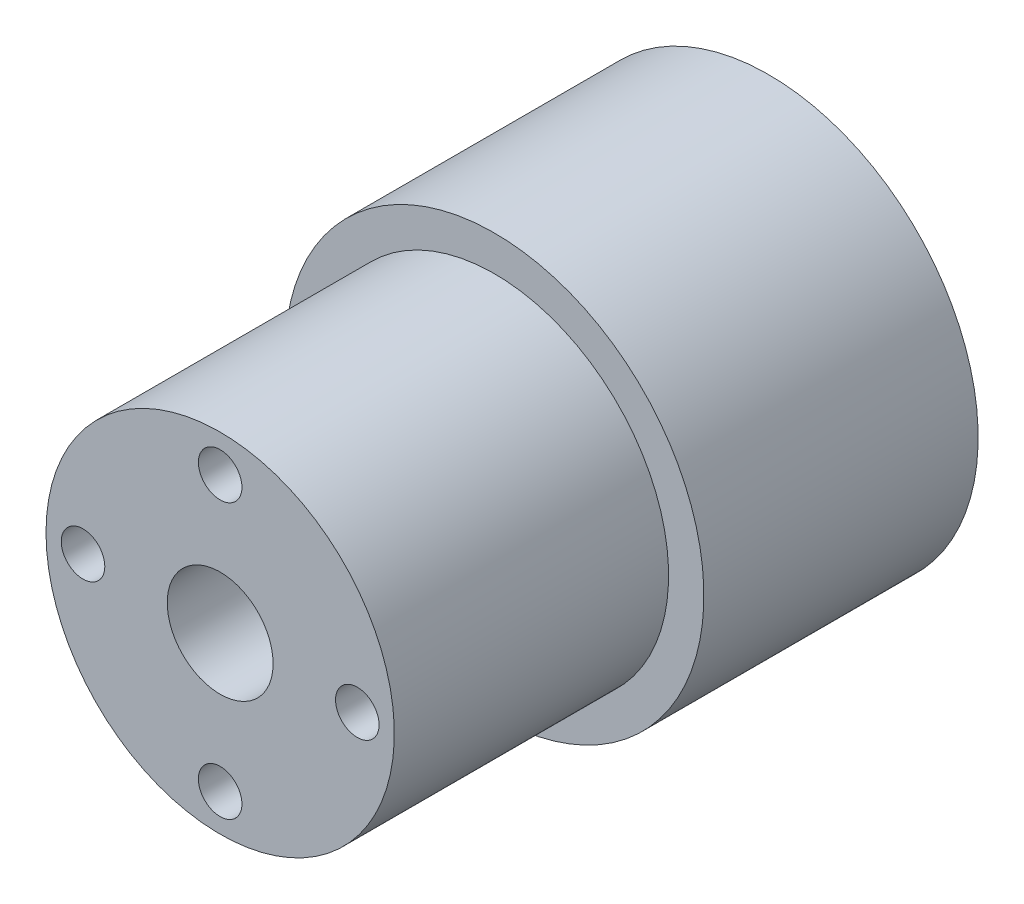
SolidWorks part; units mm, degrees
material "AISI 316 Annealed Stainless Steel Bar (SS)"
ref_plane "Front Plane" through (0, 0, 0) normal (1, 0, 0) x (0, 1, 0)
ref_plane "Top Plane" through (0, 0, 0) normal (0, 0, 1) x (0, 1, 0)
ref_plane "Right Plane" through (0, 0, 0) normal (0, 1, 0) x (-1, 0, 0)
sketch "Sketch2" plane through (0, 0, 0) normal (1, 0, 0) x (0, 1, 0)
  line L0 (0, 0) -> (9.525, 0)
  line L1 (9.525, 0) -> (9.525, -15)
  line L2 (9.525, -15) -> (11.455, -15)
  line L3 (11.455, -15) -> (11.455, -30)
  line L4 (11.455, -30) -> (0, -30)
  line L5 (0, -30) -> (0, 0)
  dimension "D1" = 9.525
  dimension "D2" = 11.455
  dimension "D3" = 15
  dimension "D4" = 30
revolve "Revolve1" add sketch "Sketch2" angle 360 about L5
sketch "Sketch1" plane through (0, 0, 0) normal (0, 0, 1) x (0, 1, 0)
  line L0 (0, 7.5) -> (0, -7.5) construction
  line L1 (-7.5, 0) -> (7.5, 0) construction
  circle A0 centre (0, 0) radius 11.455
  circle A1 centre (0, 0) radius 2.8956
  circle A2 centre (0, 7.5) radius 1.1906
  circle A3 centre (-7.5, 0) radius 1.1906
  circle A4 centre (7.5, 0) radius 1.1906
  circle A5 centre (0, -7.5) radius 1.1906
  dimension "D1" = 22.91
  dimension "D2" = 5.7912
  dimension "D3" = 2.3812
  dimension "D4" = 15
extrude "Cut-Extrude1" cut sketch "Sketch1<3>" against normal blind 8 contours A2 | A3 | A4 | A5 region at (-7.5, 0, 0) region at (0, -7.5, 0) region at (0, 7.5, 0) region at (7.5, 0, 0)
sketch "Sketch1<3>" plane through (0, 0, 0) normal (0, 0, 1) x (0, 1, 0) same geometry as "Sketch1"
extrude "Cut-Extrude2" cut sketch "Sketch1" against normal blind 16 contours A1 region at (0, 0, 0)
